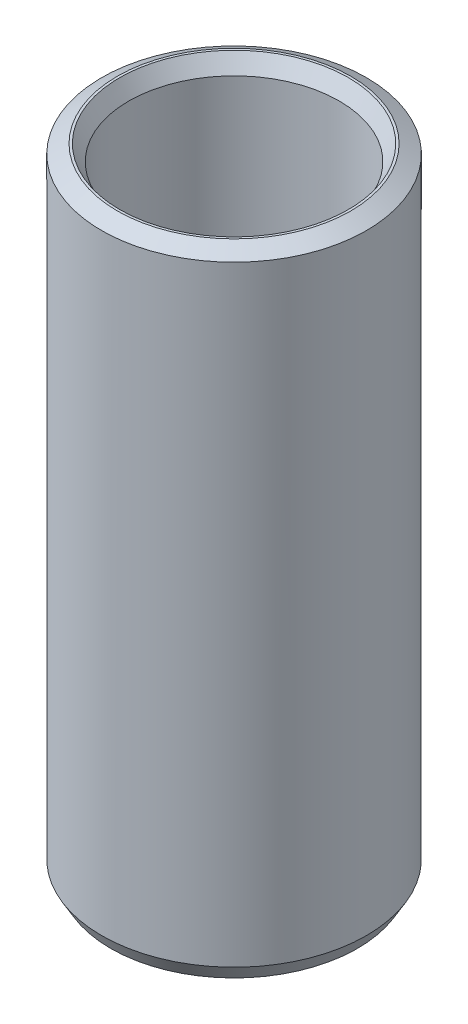
SolidWorks part; units mm, degrees
ref_plane "Front Plane" through (0, 0, 0) normal (0, 0, 1) x (1, 0, 0)
ref_plane "Top Plane" through (0, 0, 0) normal (0, 1, 0) x (1, 0, 0)
ref_plane "Right Plane" through (0, 0, 0) normal (1, 0, 0) x (0, 0, -1)
sketch "Sketch1" plane through (0, 0, 0) normal (0, 1, 0) x (1, 0, 0)
  circle A0 centre (0, 0) radius 25
  dimension "SLEEVE_OD" = 50
extrude "Boss-Extrude1" add sketch "Sketch1" along normal blind 119.9245
sketch "Sketch2" plane through (0, 0, 0) normal (0, 1, 0) x (1, 0, 0)
  circle A0 centre (0, 0) radius 19.8678
  dimension "BORE_D" = 39.7357
extrude "Cut-Extrude1" cut sketch "Sketch2" along normal through all
chamfer "Chamfer1" distance 1.7149 angle 60 4 edges at (0, 119.9245, 19.8678) (0, 0, 19.8678) (0, 0, 25) (0, 119.9245, 25) first distance on face at (0, 119.9245, 19.8678) first distance on face at (0, 0, 19.8678) first distance on face at (0, 119.9245, 25)
